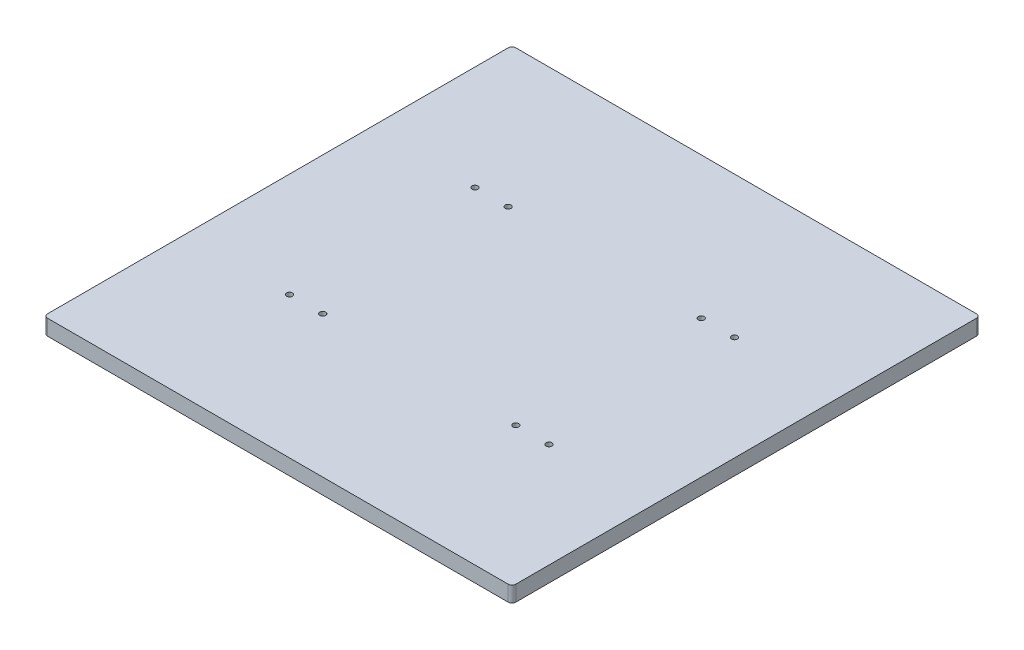
SolidWorks part; units mm, degrees
material "PMMA"
ref_plane "前视基准面" through (0, 0, 0) normal (0, 0, 1) x (1, 0, 0)
ref_plane "上视基准面" through (0, 0, 0) normal (0, 1, 0) x (1, 0, 0)
ref_plane "右视基准面" through (0, 0, 0) normal (1, 0, 0) x (0, 0, -1)
sketch "草图1" plane through (0, 0, 0) normal (0, 1, 0) x (1, 0, 0)
  line L1 (-118, -120) -> (118, -120)
  line L2 (-120, -118) -> (-120, 118)
  line L3 (-118, 120) -> (118, 120)
  line L4 (120, -118) -> (120, 118)
  line L5 (-120, -120) -> (120, 120) construction
  line L6 (-120, 120) -> (120, -120) construction
  arc A0 (120, -118) -> (118, -120) centre (118, -118) cw
  arc A1 (-118, -120) -> (-120, -118) centre (-118, -118) cw
  arc A2 (120, 118) -> (118, 120) centre (118, 118) ccw
  arc A3 (-118, 120) -> (-120, 118) centre (-118, 118) ccw
  point P0 (0, 0)
  dimension "D3" = 2
  dimension "D1" = 240
  dimension "D2" = 240
extrude "凸台-拉伸1" add sketch "草图1" against normal blind 8
sketch "Sketch2" plane through (0, -8, 0) normal (0, -1, 0) x (1, 0, 0)
  line L0 (0, -120) -> (0, 165.2098) construction
  line L1 (118, -120) -> (-118, -120) construction
  line L2 (-120, 0) -> (120, 0) construction
  line L3 (-120, -118) -> (-120, 118) construction
  line L4 (120, 118) -> (120, -118) construction
  line L5 (-66.5, -47.5) -> (-66.5, 47.5) construction
  line L6 (-66.5, 47.5) -> (-49.5, 47.5) construction
  line L7 (-49.5, 47.5) -> (-49.5, -47.5) construction
  line L8 (-66.5, -47.5) -> (-49.5, -47.5) construction
  line L9 (66.5, -47.5) -> (49.5, -47.5) construction
  line L10 (49.5, 47.5) -> (49.5, -47.5) construction
  line L11 (66.5, 47.5) -> (49.5, 47.5) construction
  line L12 (66.5, -47.5) -> (66.5, 47.5) construction
  circle A0 centre (-66.5, 47.5) radius 1.5
  circle A1 centre (-49.5, 47.5) radius 1.5
  circle A2 centre (-66.5, -47.5) radius 1.5
  circle A3 centre (-49.5, -47.5) radius 1.5
  circle A4 centre (49.5, -47.5) radius 1.5
  circle A5 centre (66.5, -47.5) radius 1.5
  circle A6 centre (49.5, 47.5) radius 1.5
  circle A7 centre (66.5, 47.5) radius 1.5
  point P16 (-49.5, 0)
  point P17 (-66.5, 0)
  point P29 (66.5, 0)
  point P30 (49.5, 0)
  dimension "D4" = 3
  dimension "D5" = 3
  dimension "D6" = 3
  dimension "D7" = 3
  dimension "D1" = 47.5
  dimension "D2" = 17
  dimension "D3" = 66.5
extrude "Cut-Extrude1" cut sketch "Sketch2" against normal through all
